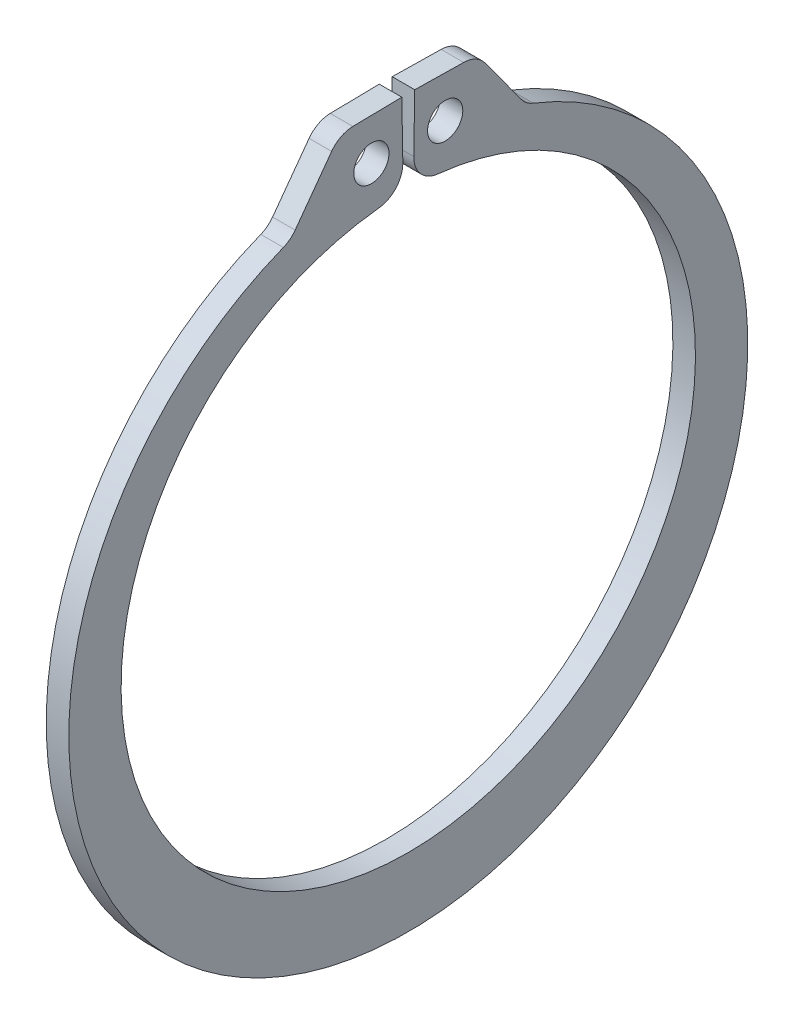
SolidWorks part; units mm, degrees
material "Cast Carbon Steel"
ref_plane "Front" through (0, 0, 0) normal (0, 0, 1) x (1, 0, 0)
ref_plane "Top" through (0, 0, 0) normal (0, 1, 0) x (1, 0, 0)
ref_plane "Right" through (0, 0, 0) normal (1, 0, 0) x (0, 0, -1)
sketch "Sketch1" plane through (0, 0, 0) normal (1, 0, 0) x (0, 0, -1)
  line L0 (0, 0) -> (0, 16.1544) construction
  line L1 (-0.2819, 16.1519) -> (-0.3635, 20.8248)
  line L2 (0.3635, 20.8248) -> (3.8682, 20.7637)
  line L3 (3.8682, 20.7637) -> (6.6264, 16.9908)
  line L4 (0.2819, 16.1519) -> (0.3635, 20.8248)
  line L5 (-0.3635, 20.8248) -> (-3.8682, 20.7637)
  line L6 (-3.8682, 20.7637) -> (-6.6264, 16.9908)
  line L7 (-6.6264, 16.9908) -> (-5.8696, 15.0503) construction
  line L8 (6.6264, 16.9908) -> (5.8696, 15.0503) construction
  line L9 (0, -16.1544) -> (0, -20.0152) construction
  line L10 (-3.8682, 20.7637) -> (-0.2819, 16.1519) construction
  line L11 (0, 16.1544) -> (0, 20.828) construction
  line L12 (-16.1544, 0) -> (16.1544, 0) construction
  circle A0 centre (0, 0) radius 16.1544 construction
  arc A1 (-0.2819, 16.1519) -> (0.2819, 16.1519) centre (0, 0) ccw
  circle A4 centre (-2.075, 18.4578) radius 0.9906
  circle A5 centre (2.075, 18.4578) radius 0.9906
  arc A6 (-6.6264, 16.9908) -> (6.6264, 16.9908) centre (0, -0.9189) ccw construction
  point P0 (0, -20.0152)
  dimension "Ring ID" = 32.3088
  dimension "Hole Diameter" = 1.9812
  dimension "Min. Sec." = 2.0828
  dimension "Max. Sec." = 3.8608
  dimension "Lug Height" = 4.6736
  dimension "D2" = 3.5052
  dimension "Angle" = 1
sketch "Sketch2" plane through (0, 0, 0) normal (0, 1, 0) x (1, 0, 0)
  line L0 (-0.635, -19.0741) -> (0.635, -19.0741) construction
  line L1 (0, -19.0963) -> (0, 19.0963) construction
  point P8 (0, -19.0741)
  dimension "Ring Thickness" = 1.27
sketch "Sketch3" plane through (0, 0, 0) normal (1, 0, 0) x (0, 0, -1)
  line L0 (-3.8682, 20.7637) -> (-6.6264, 16.9908) construction
  line L1 (-3.8682, 20.7637) -> (-6.6264, 16.9908)
  line L2 (-0.3635, 20.8248) -> (-3.8682, 20.7637) construction
  line L3 (-0.3635, 20.8248) -> (-3.8682, 20.7637)
  line L4 (-0.2819, 16.1519) -> (-0.3635, 20.8248) construction
  line L5 (-0.2819, 16.1519) -> (-0.3635, 20.8248)
  line L6 (0.2819, 16.1519) -> (0.3635, 20.8248) construction
  line L7 (0.2819, 16.1519) -> (0.3635, 20.8248)
  line L8 (0.3635, 20.8248) -> (3.8682, 20.7637) construction
  line L9 (0.3635, 20.8248) -> (3.8682, 20.7637)
  line L10 (3.8682, 20.7637) -> (6.6264, 16.9908) construction
  line L11 (3.8682, 20.7637) -> (6.6264, 16.9908)
  arc A0 (-6.6264, 16.9908) -> (6.6264, 16.9908) centre (0, -0.9189) ccw construction
  arc A1 (-6.6264, 16.9908) -> (6.6264, 16.9908) centre (0, -0.9189) ccw
  arc A2 (-0.2819, 16.1519) -> (0.2819, 16.1519) centre (0, 0) ccw construction
  arc A3 (-0.2819, 16.1519) -> (0.2819, 16.1519) centre (0, 0) ccw
  circle A4 centre (-2.075, 18.4578) radius 0.9906 construction
  circle A5 centre (-2.075, 18.4578) radius 0.9906
  circle A6 centre (2.075, 18.4578) radius 0.9906 construction
  circle A7 centre (2.075, 18.4578) radius 0.9906
extrude "Boss-Extrude1" add sketch "Sketch3" along normal up to vertex (0.635 mm away) and the other way up to vertex (0.635 mm away) up to point (0.635, 0, 19.0741) other way up to point (-0.635, 0, 19.0741)
fillet "Fillet1" radius 1.5113 6 edges at (0, 16.9908, -6.6264) (0, 20.7637, -3.8682) (0, 16.1519, -0.2819) (0, 16.1519, 0.2819) (0, 20.7637, 3.8682) (0, 16.9908, 6.6264)
sketch "Sketch4" plane through (0, 0, 0) normal (1, 0, 0) x (0, 0, -1)
  line L0 (-13.9901, 8.0772) -> (0, 0) construction
  line L1 (0, 0) -> (0, 16.1544) construction
  line L2 (0, 20.828) -> (0, 16.1544) construction
  arc A0 (-0.2819, 16.1519) -> (0.2819, 16.1519) centre (0, 0) ccw construction
  point P0 (0, 0)
  point P1 (-13.9901, 8.0772)
  dimension "D1" = 60
equation "\"D2@Sketch1\" = \"Lug Height@Sketch1\" * .75"
